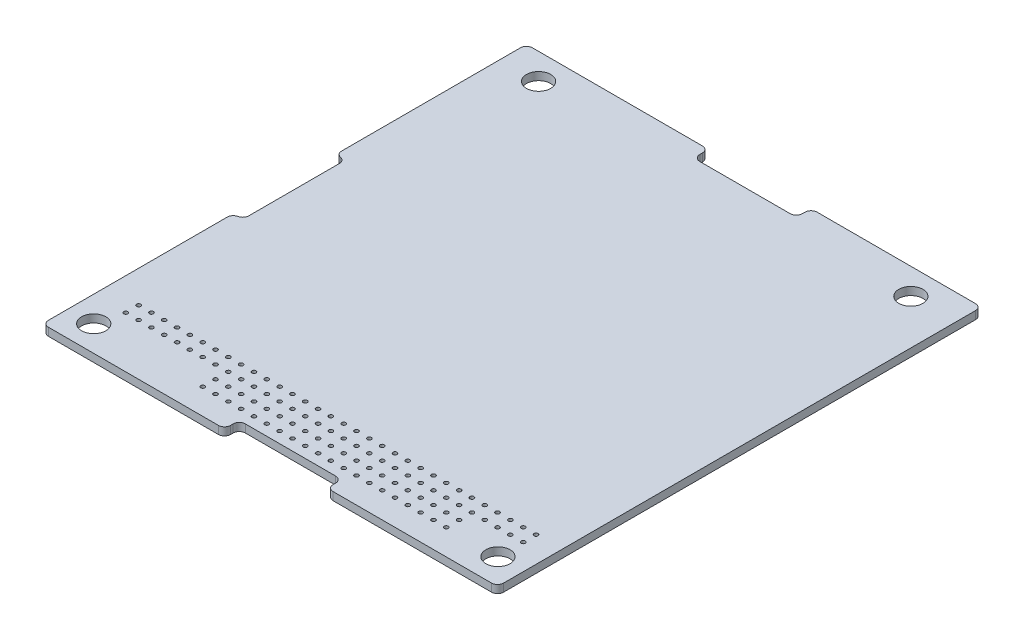
SolidWorks part; units mm, degrees
ref_plane "Front Plane" through (0, 0, 0) normal (0, 0, 1) x (1, 0, 0)
ref_plane "Top Plane" through (0, 0, 0) normal (0, 1, 0) x (1, 0, 0)
ref_plane "Right Plane" through (0, 0, 0) normal (1, 0, 0) x (0, 0, -1)
sketch "Sketch1" plane through (0, 0, 0) normal (0, 1, 0) x (1, 0, 0)
  line L1 (-45.085, -47.945) -> (45.085, -47.945)
  line L2 (-45.085, -47.945) -> (-45.085, 47.945)
  line L3 (-45.085, 47.945) -> (45.085, 47.945)
  line L4 (45.085, -47.945) -> (45.085, 47.945)
  line L5 (-45.085, -47.945) -> (45.085, 47.945) construction
  line L6 (-45.085, 47.945) -> (45.085, -47.945) construction
  point P0 (0, 0)
  dimension "D1" = 95.89
  dimension "D2" = 90.17
extrude "Boss-Extrude1" add sketch "Sketch1" along normal blind 1.57
sketch "Sketch2" plane through (0, 1.57, 0) normal (0, 1, 0) x (1, 0, 0)
  line L0 (-45.085, 47.945) -> (-9.015, 47.945) construction
  line L1 (45.085, 47.945) -> (-45.085, 47.945) construction
  line L2 (-45.085, -47.945) -> (-45.085, -10.135) construction
  line L3 (-9.015, 47.945) -> (11.305, 47.945)
  line L4 (-9.015, 47.945) -> (-9.015, 45.015)
  line L5 (-9.015, 45.015) -> (11.305, 45.015)
  line L6 (11.305, 47.945) -> (11.305, 45.015)
  line L7 (-45.085, 47.945) -> (-45.085, -47.945) construction
  line L8 (-45.085, -47.945) -> (-9.015, -47.945) construction
  line L9 (-45.085, -10.135) -> (-43.165, -10.135)
  line L10 (-45.085, -10.135) -> (-45.085, 10.135)
  line L11 (-45.085, 10.135) -> (-43.165, 10.135)
  line L12 (-43.165, -10.135) -> (-43.165, 10.135)
  line L13 (-45.085, -47.945) -> (45.085, -47.945) construction
  line L15 (-9.015, -47.945) -> (11.305, -47.945)
  line L16 (-9.015, -47.945) -> (-9.015, -45.025)
  line L17 (-9.015, -45.025) -> (11.305, -45.025)
  line L18 (11.305, -47.945) -> (11.305, -45.025)
  dimension "D1" = 36.07
  dimension "D2" = 20.32
  dimension "D3" = 2.93
  dimension "D4" = 37.81
  dimension "D5" = 20.27
  dimension "D6" = 1.92
  dimension "D7" = 2.92
extrude "Cut-Extrude1" cut sketch "Sketch2" against normal blind 1.57
sketch "Sketch3" plane through (0, 1.57, 0) normal (0, 1, 0) x (1, 0, 0)
  line L0 (-45.085, -47.945) -> (-40.005, -47.945) construction
  line L1 (-45.085, -47.945) -> (-9.015, -47.945) construction
  line L2 (-40.005, -47.945) -> (-40.005, -42.865) construction
  line L3 (45.085, -47.945) -> (40.005, -47.945) construction
  line L4 (11.305, -47.945) -> (45.085, -47.945) construction
  line L5 (40.005, -47.945) -> (40.005, -42.785) construction
  line L6 (-45.085, 47.945) -> (-37.515, 47.945) construction
  line L7 (-9.015, 47.945) -> (-45.085, 47.945) construction
  line L8 (-37.515, 47.945) -> (-37.515, 42.785) construction
  line L9 (45.085, 47.945) -> (11.305, 47.945) construction
  line L10 (11.305, -47.945) -> (45.085, -47.945) construction
  line L11 (45.085, -47.945) -> (45.085, 47.945) construction
  line L12 (-45.085, 47.945) -> (-45.085, 10.135) construction
  circle A0 centre (-40.005, -42.865) radius 2.4
  circle A1 centre (40.005, -42.785) radius 2.4
  circle A2 centre (-37.515, 42.785) radius 2.4
  circle A3 centre (36.235, 42.785) radius 2.4
  dimension "D3" = 4.8
  dimension "D6" = 5.16
  dimension "D4" = 5.08
  dimension "D5" = 4.8
  dimension "D7" = 4.8
  dimension "D8" = 4.8
  dimension "D1" = 5.08
  dimension "D2" = 5.08
  dimension "D9" = 5.16
  dimension "D10" = 5.16
  dimension "D11" = 8.85
  dimension "7.85mm" = 7.57
extrude "Cut-Extrude2" cut sketch "Sketch3" against normal blind 1.57
fillet "Fillet7" radius 1.2 1 edges at (-9.015, 0.785, 45.025)
fillet "Fillet8" radius 1.2 1 edges at (-9.015, 0.785, 47.945)
fillet "Fillet9" radius 1.2 2 edges at (11.305, 0.785, 47.945) (11.305, 0.785, 45.025)
fillet "Fillet10" radius 1.2 1 edges at (45.085, 0.785, 47.945)
fillet "Fillet11" radius 1.2 1 edges at (45.085, 0.785, -47.945)
fillet "Fillet12" radius 1.2 2 edges at (11.305, 0.785, -45.015) (11.305, 0.785, -47.945)
fillet "Fillet13" radius 1.2 2 edges at (-9.015, 0.785, -47.945) (-9.015, 0.785, -45.015)
fillet "Fillet14" radius 1.2 1 edges at (-45.085, 0.785, -47.945)
fillet "Fillet17" radius 1.2 1 edges at (-45.085, 0.785, -10.135)
fillet "Fillet18" radius 1.2 1 edges at (-43.165, 0.785, -10.135)
fillet "Fillet19" radius 1.2 1 edges at (-45.085, 0.785, 10.135)
fillet "Fillet20" radius 1.2 1 edges at (-43.165, 0.785, 10.135)
fillet "Fillet21" radius 1.2 1 edges at (-45.085, 0.785, 47.945)
sketch "Sketch11" plane through (0, 1.57, 0) normal (0, 1, 0) x (1, 0, 0)
  line L0 (-43.885, -47.945) -> (-45.2926, -47.945) construction
  line L1 (-45.085, -46.745) -> (-45.085, -47.945) construction
  line L2 (-45.085, -47.945) -> (-38.735, -47.945) construction
  line L3 (-43.885, -47.945) -> (-10.215, -47.945) construction
  line L4 (-38.735, -47.945) -> (-38.735, -37.785) construction
  circle A0 centre (-38.735, -37.785) radius 0.4
  circle A1 centre (-36.195, -37.785) radius 0.4
  circle A2 centre (-33.655, -37.785) radius 0.4
  circle A3 centre (-31.115, -37.785) radius 0.4
  circle A4 centre (-28.575, -37.785) radius 0.4
  circle A5 centre (-26.035, -37.785) radius 0.4
  circle A6 centre (-23.495, -37.785) radius 0.4
  circle A7 centre (-20.955, -37.785) radius 0.4
  circle A8 centre (-18.415, -37.785) radius 0.4
  circle A9 centre (-15.875, -37.785) radius 0.4
  circle A10 centre (-13.335, -37.785) radius 0.4
  circle A11 centre (-10.795, -37.785) radius 0.4
  circle A12 centre (-8.255, -37.785) radius 0.4
  circle A13 centre (-5.715, -37.785) radius 0.4
  circle A14 centre (-3.175, -37.785) radius 0.4
  circle A15 centre (-0.635, -37.785) radius 0.4
  circle A16 centre (1.905, -37.785) radius 0.4
  circle A17 centre (4.445, -37.785) radius 0.4
  circle A18 centre (6.985, -37.785) radius 0.4
  circle A19 centre (9.525, -37.785) radius 0.4
  circle A20 centre (12.065, -37.785) radius 0.4
  circle A21 centre (14.605, -37.785) radius 0.4
  circle A22 centre (17.145, -37.785) radius 0.4
  circle A23 centre (19.685, -37.785) radius 0.4
  circle A24 centre (22.225, -37.785) radius 0.4
  circle A25 centre (24.765, -37.785) radius 0.4
  circle A26 centre (27.305, -37.785) radius 0.4
  circle A27 centre (29.845, -37.785) radius 0.4
  circle A28 centre (32.385, -37.785) radius 0.4
  circle A29 centre (34.925, -37.785) radius 0.4
  circle A30 centre (37.465, -37.785) radius 0.4
  circle A31 centre (40.005, -37.785) radius 0.4
  dimension "D3" = 0.8
  dimension "D1" = 6.35
  dimension "D2" = 10.16
  dimension "D4" = 32
extrude "Cut-Extrude8" cut sketch "Sketch11" against normal blind 10
sketch "Sketch12" plane through (0, 1.57, 0) normal (0, 1, 0) x (1, 0, 0)
  line L0 (-38.735, -37.785) -> (-38.735, -35.245) construction
  circle A0 centre (-38.735, -35.245) radius 0.4
  circle A1 centre (-36.195, -35.245) radius 0.4
  circle A2 centre (-33.655, -35.245) radius 0.4
  circle A3 centre (-31.115, -35.245) radius 0.4
  circle A4 centre (-28.575, -35.245) radius 0.4
  circle A5 centre (-26.035, -35.245) radius 0.4
  circle A6 centre (-23.495, -35.245) radius 0.4
  circle A7 centre (-20.955, -35.245) radius 0.4
  circle A8 centre (-18.415, -35.245) radius 0.4
  circle A9 centre (-15.875, -35.245) radius 0.4
  circle A10 centre (-13.335, -35.245) radius 0.4
  circle A11 centre (-10.795, -35.245) radius 0.4
  circle A12 centre (-8.255, -35.245) radius 0.4
  circle A13 centre (-5.715, -35.245) radius 0.4
  circle A14 centre (-3.175, -35.245) radius 0.4
  circle A15 centre (-0.635, -35.245) radius 0.4
  circle A16 centre (1.905, -35.245) radius 0.4
  circle A17 centre (4.445, -35.245) radius 0.4
  circle A18 centre (6.985, -35.245) radius 0.4
  circle A19 centre (9.525, -35.245) radius 0.4
  circle A20 centre (12.065, -35.245) radius 0.4
  circle A21 centre (14.605, -35.245) radius 0.4
  circle A22 centre (17.145, -35.245) radius 0.4
  circle A23 centre (19.685, -35.245) radius 0.4
  circle A24 centre (22.225, -35.245) radius 0.4
  circle A25 centre (24.765, -35.245) radius 0.4
  circle A26 centre (27.305, -35.245) radius 0.4
  circle A27 centre (29.845, -35.245) radius 0.4
  circle A28 centre (32.385, -35.245) radius 0.4
  circle A29 centre (34.925, -35.245) radius 0.4
  circle A30 centre (37.465, -35.245) radius 0.4
  circle A31 centre (40.005, -35.245) radius 0.4
  dimension "D2" = 0.8
  dimension "D1" = 2.54
  dimension "D3" = 32
extrude "Cut-Extrude9" cut sketch "Sketch12" against normal blind 10
sketch "Sketch13" plane through (0, 1.57, 0) normal (0, 1, 0) x (1, 0, 0)
  line L0 (-43.885, -47.945) -> (-45.085, -47.945) construction
  line L1 (-45.085, -47.945) -> (-45.085, -46.745) construction
  line L2 (-45.085, -47.945) -> (-18.415, -47.945) construction
  line L3 (-43.885, -47.945) -> (-10.215, -47.945) construction
  line L4 (-18.415, -47.945) -> (-18.415, -42.865) construction
  circle A0 centre (-18.415, -42.865) radius 0.4
  circle A1 centre (-15.875, -42.865) radius 0.4
  circle A2 centre (-13.335, -42.865) radius 0.4
  circle A3 centre (-10.795, -42.865) radius 0.4
  circle A4 centre (-8.255, -42.865) radius 0.4
  circle A5 centre (-5.715, -42.865) radius 0.4
  circle A6 centre (-3.175, -42.865) radius 0.4
  circle A7 centre (-0.635, -42.865) radius 0.4
  circle A8 centre (1.905, -42.865) radius 0.4
  circle A9 centre (4.445, -42.865) radius 0.4
  circle A10 centre (6.985, -42.865) radius 0.4
  circle A11 centre (9.525, -42.865) radius 0.4
  circle A12 centre (12.065, -42.865) radius 0.4
  circle A13 centre (14.605, -42.865) radius 0.4
  circle A14 centre (17.145, -42.865) radius 0.4
  circle A15 centre (19.685, -42.865) radius 0.4
  circle A16 centre (22.225, -42.865) radius 0.4
  circle A17 centre (24.765, -42.865) radius 0.4
  circle A18 centre (27.305, -42.865) radius 0.4
  circle A19 centre (29.845, -42.865) radius 0.4
  dimension "D3" = 0.8
  dimension "D1" = 26.67
  dimension "D2" = 5.08
  dimension "D4" = 20
extrude "Cut-Extrude10" cut sketch "Sketch13" against normal blind 10
sketch "Sketch14" plane through (0, 1.57, 0) normal (0, 1, 0) x (1, 0, 0)
  line L0 (-18.415, -42.865) -> (-18.415, -40.325) construction
  circle A0 centre (-18.415, -40.325) radius 0.4
  circle A1 centre (-15.875, -40.325) radius 0.4
  circle A2 centre (-13.335, -40.325) radius 0.4
  circle A3 centre (-10.795, -40.325) radius 0.4
  circle A4 centre (-8.255, -40.325) radius 0.4
  circle A5 centre (-5.715, -40.325) radius 0.4
  circle A6 centre (-3.175, -40.325) radius 0.4
  circle A7 centre (-0.635, -40.325) radius 0.4
  circle A8 centre (1.905, -40.325) radius 0.4
  circle A9 centre (4.445, -40.325) radius 0.4
  circle A10 centre (6.985, -40.325) radius 0.4
  circle A11 centre (9.525, -40.325) radius 0.4
  circle A12 centre (12.065, -40.325) radius 0.4
  circle A13 centre (14.605, -40.325) radius 0.4
  circle A14 centre (17.145, -40.325) radius 0.4
  circle A15 centre (19.685, -40.325) radius 0.4
  circle A16 centre (22.225, -40.325) radius 0.4
  circle A17 centre (24.765, -40.325) radius 0.4
  circle A18 centre (27.305, -40.325) radius 0.4
  circle A19 centre (29.845, -40.325) radius 0.4
  dimension "D2" = 0.8
  dimension "D1" = 2.54
  dimension "D3" = 20
extrude "Cut-Extrude11" cut sketch "Sketch14" against normal blind 10
